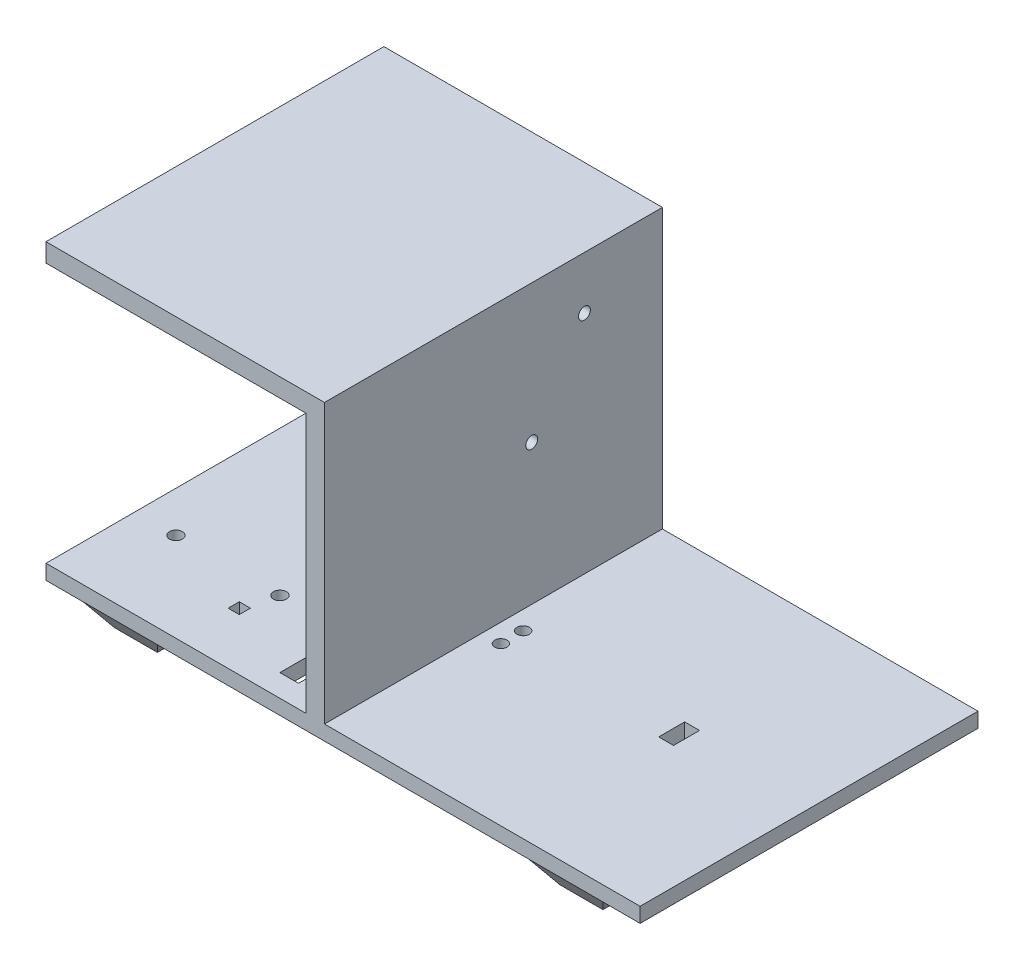
SolidWorks part; units mm, degrees
ref_plane "Front Plane" through (0, 0, 0) normal (0, 0, 1) x (1, 0, 0)
ref_plane "Top Plane" through (0, 0, 0) normal (0, 1, 0) x (1, 0, 0)
ref_plane "Right Plane" through (0, 0, 0) normal (1, 0, 0) x (0, 0, -1)
sketch "Sketch1" plane through (0, 0, 0) normal (0, 0, 1) x (1, 0, 0)
  line L1 (0, 0) -> (160, 0)
  line L2 (0, 0) -> (0, 4)
  line L3 (0, 4) -> (160, 4)
  line L4 (160, 0) -> (160, 4)
  dimension "D1" = 4
  dimension "D2" = 160
extrude "Boss-Extrude1" add sketch "Sketch1" against normal blind 91
sketch "Sketch2" plane through (0, 0, 0) normal (0, 0, 1) x (1, 0, 0)
  line L0 (0, 4) -> (70, 4) construction
  line L1 (160, 4) -> (0, 4) construction
  line L3 (70, 4) -> (75, 4)
  line L4 (70, 4) -> (70, 79)
  line L5 (70, 79) -> (75, 79)
  line L6 (75, 4) -> (75, 79)
  dimension "D1" = 5
  dimension "D2" = 75
extrude "Boss-Extrude2" add sketch "Sketch2" against normal up to surface (91 mm away) up to face at (80, 2, -91)
sketch "Sketch3" plane through (70, 0, 0) normal (-1, 0, 0) x (0, 0, 1)
  line L0 (0, 79) -> (0, 4) construction
  line L1 (-91, 79) -> (0, 79)
  line L2 (-91, 79) -> (-91, 74)
  line L3 (-91, 74) -> (0, 74)
  line L4 (0, 79) -> (0, 74)
  dimension "D1" = 5
extrude "Boss-Extrude3" add sketch "Sketch3" along normal up to surface (70 mm away) up to face at (0, 2, -45.5)
sketch "Sketch4" plane through (0, 4, 0) normal (0, 1, 0) x (1, 0, 0)
  line L0 (70, 91) -> (70, 0) construction
  line L1 (57, 13) -> (62, 13)
  line L2 (57, 13) -> (57, 6)
  line L3 (57, 6) -> (62, 6)
  line L4 (62, 13) -> (62, 6)
  line L5 (70, 0) -> (0, 0) construction
  dimension "D1" = 8
  dimension "D2" = 6
  dimension "D3" = 5
  dimension "D4" = 7
extrude "Cut-Extrude1" cut sketch "Sketch4" against normal blind 91
sketch "Sketch5" plane through (0, 4, 0) normal (0, 1, 0) x (1, 0, 0)
  line L0 (75, 91) -> (0, 91) construction
  line L1 (0, 0) -> (0, 91) construction
  circle A0 centre (11, 24) radius 1.75
  circle A1 centre (39, 24) radius 1.75
  circle A2 centre (6, 76) radius 1.75
  point P8 (9.4684, 75.4831)
  dimension "D1" = 28
  dimension "D3" = 52
  dimension "D6" = 3.5
  dimension "D7" = 3.5
  dimension "D8" = 3.5
  dimension "D2" = 67
  dimension "D4" = 5
  dimension "D5" = 11
extrude "Cut-Extrude2" cut sketch "Sketch5" against normal blind 91
sketch "Sketch6" plane through (0, 4, 0) normal (0, 1, 0) x (1, 0, 0)
  line L0 (70, 91) -> (70, 0) construction
  line L1 (35, 17.0487) -> (38, 17.0487)
  line L2 (35, 17.0487) -> (35, 14.0487)
  line L3 (35, 14.0487) -> (38, 14.0487)
  line L4 (38, 17.0487) -> (38, 14.0487)
  dimension "D1" = 3
  dimension "D2" = 3
  dimension "D3" = 32
extrude "Cut-Extrude3" cut sketch "Sketch6" against normal blind 91
sketch "Sketch7" plane through (0, 4, 0) normal (0, 1, 0) x (1, 0, 0)
  line L1 (160, 91) -> (75, 91) construction
  line L2 (75, 91) -> (75, 0) construction
  line L4 (160, 0) -> (75, 0) construction
  circle A0 centre (80, 48.5) radius 1.65
  circle A1 centre (80, 42.5) radius 1.65
  dimension "D1" = 3.3
  dimension "D2" = 3.3
  dimension "D3" = 6
  dimension "D4" = 42.5
  dimension "D5" = 5
  dimension "D6" = 42.5
extrude "Cut-Extrude4" cut sketch "Sketch7" against normal blind 91
sketch "Sketch8" plane through (0, 0, 0) normal (0, -1, 0) x (1, 0, 0)
  line L0 (0, 0) -> (160, 0) construction
  line L1 (10, 0) -> (30, 0)
  line L2 (10, 0) -> (10, -20)
  line L3 (10, -20) -> (30, -20)
  line L4 (30, 0) -> (30, -20)
  line L5 (0, -91) -> (0, 0) construction
  dimension "D1" = 20
  dimension "D2" = 20
  dimension "D3" = 10
extrude "Boss-Extrude4" add sketch "Sketch8" along normal blind 6
chamfer "Chamfer1" distance 6 angle 35 4 edges at (30, -6, -10) (20, -6, -20) (10, -6, -10) (20, -6, 0) first distance on face at (30, -3, -10) first distance on face at (20, -3, -20) first distance on face at (10, -3, -10) first distance on face at (49.2857, 22.1429, 0)
sketch "Sketch9" plane through (0, 0, 0) normal (0, -1, 0) x (1, 0, 0)
  line L0 (0, -91) -> (160, -91) construction
  line L1 (10, -91) -> (30, -91)
  line L2 (10, -91) -> (10, -71)
  line L3 (10, -71) -> (30, -71)
  line L4 (30, -91) -> (30, -71)
  line L5 (0, -91) -> (0, 0) construction
  line L6 (130, -91) -> (130, -71)
  line L7 (130, -91) -> (150, -91)
  line L8 (150, -91) -> (150, -71)
  line L9 (130, -71) -> (150, -71)
  line L10 (130, -20) -> (130, 0)
  line L11 (130, 0) -> (150, 0)
  line L12 (150, -20) -> (150, 0)
  line L13 (130, -20) -> (150, -20)
  dimension "D1" = 20
  dimension "D2" = 20
  dimension "D3" = 10
  dimension "D4" = 2
  dimension "D5" = 2
extrude "Boss-Extrude5" add sketch "Sketch9" along normal blind 6
chamfer "Chamfer2" distance 6 angle 35 12 edges at (30, -6, -81) (20, -6, -91) (10, -6, -81) (20, -6, -71) (140, -6, -91) (150, -6, -81) (130, -6, -81) (140, -6, -71) (130, -6, -10) (140, -6, -20) (150, -6, -10) (140, -6, 0) first distance on face at (30, -3, -81) first distance on face at (69.4444, 16.5556, -91) first distance on face at (10, -3, -81) first distance on face at (20, -3, -71) first distance on face at (150, -3, -81) first distance on face at (130, -3, -81) first distance on face at (140, -3, -71) first distance on face at (130, -3, -10) first distance on face at (140, -3, -20) first distance on face at (150, -3, -10) first distance on face at (75.625, 19.375, 0)
sketch "Sketch10" plane through (0, 4, 0) normal (0, 1, 0) x (1, 0, 0)
  line L0 (127, 45.5) -> (123, 45.5) construction
  line L1 (123, 49) -> (127, 49)
  line L2 (123, 49) -> (123, 42)
  line L3 (123, 42) -> (127, 42)
  line L4 (127, 49) -> (127, 42)
  line L5 (160, 91) -> (75, 91) construction
  line L6 (125, 49) -> (125, 42) construction
  circle A2 centre (80, 48.5) radius 1.65 construction
  dimension "D1" = 4
  dimension "D2" = 7
  dimension "D3" = 45.5
  dimension "D4" = 45
extrude "Cut-Extrude5" cut sketch "Sketch10" against normal blind 6
sketch "Sketch11" plane through (70, 0, 0) normal (-1, 0, 0) x (0, 0, 1)
  line L0 (-91, 74) -> (-91, 4) construction
  circle A0 centre (-70, 64.802) radius 1.6
  circle A2 centre (-55.8, 41.802) radius 1.6
  dimension "D1" = 23
  dimension "D2" = 3.2
  dimension "D4" = 3.2
  dimension "D3" = 14.2
  dimension "D5" = 21
extrude "Cut-Extrude6" cut sketch "Sketch11" against normal blind 6
